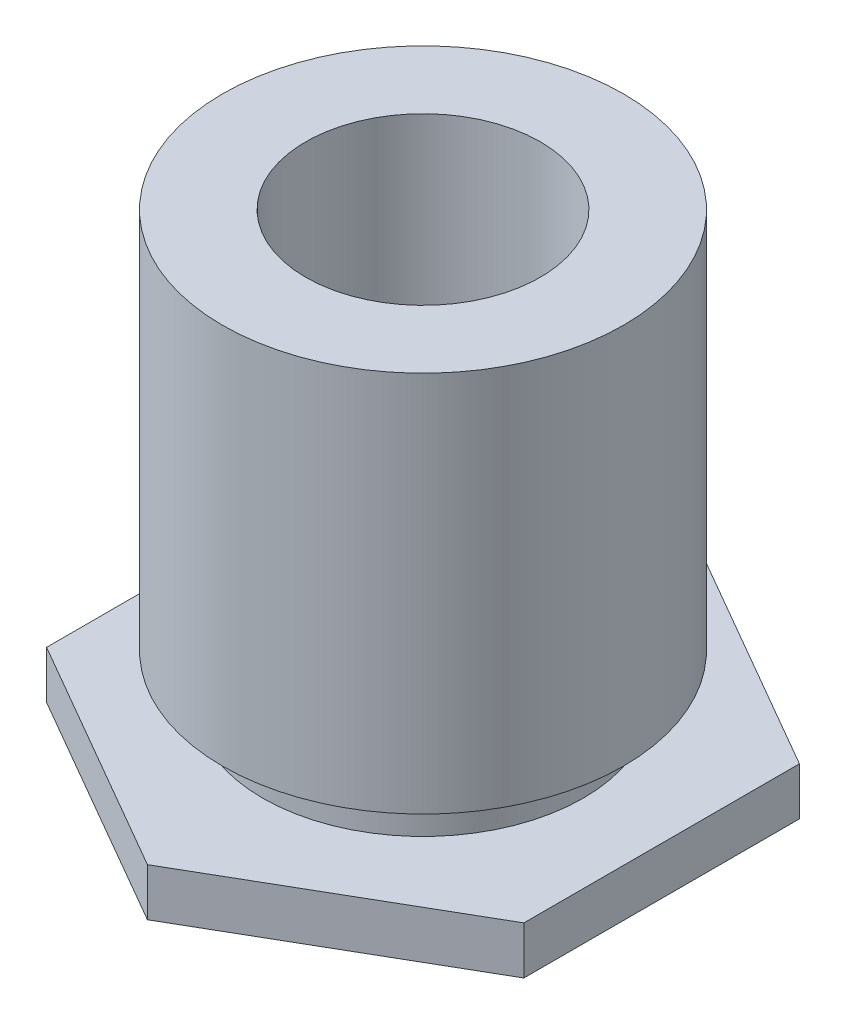
SolidWorks part; units mm, degrees
other "Детальный элемент1"
other "Детальный элемент2"
material "A2"
ref_plane "Спереди" through (0, 0, 0) normal (0, 0, 1) x (1, 0, 0)
ref_plane "Сверху" through (0, 0, 0) normal (0, 1, 0) x (1, 0, 0)
ref_plane "Справа" through (0, 0, 0) normal (1, 0, 0) x (0, 0, -1)
sketch "Эскиз1" plane through (0, 0, 0) normal (0, 1, 0) x (1, 0, 0)
  line L1 (0, -2.8868) -> (2.5, -1.4434)
  line L2 (2.5, -1.4434) -> (2.5, 1.4434)
  line L3 (2.5, 1.4434) -> (0, 2.8868)
  line L4 (0, 2.8868) -> (-2.5, 1.4434)
  line L5 (-2.5, 1.4434) -> (-2.5, -1.4434)
  line L6 (-2.5, -1.4434) -> (0, -2.8868)
  circle A0 centre (0, 0) radius 2.5 construction
  dimension "Размер шестигранника шляпки" = 5
extrude "Бобышка-Вытянуть1" add sketch "Эскиз1" along normal blind 0.5
sketch "Эскиз6" plane through (0, 0, 0) normal (0, 0, 1) x (1, 0, 0)
  line L0 (2.1, 5) -> (2.1, 1)
  line L1 (2.1, 1) -> (1.68, 1)
  line L2 (1.68, 1) -> (1.68, 0.5)
  line L3 (0, 0.5) -> (2.5, 0.5) construction
  line L4 (1.68, 0.5) -> (0, 0.5)
  line L5 (0, 0.5) -> (0, 1.8)
  line L6 (0, 1.8) -> (1.2295, 1.8)
  line L7 (1.2295, 1.8) -> (1.2295, 5)
  line L8 (1.2295, 5) -> (2.1, 5)
  line L9 (0, 1.8) -> (0, 0) construction
  line L10 (2.5, 0.5) -> (2.5, 0) construction
  line L11 (0, 0) -> (2.5, 0) construction
  dimension "D1" = 3.36
  dimension "Внешний диаметр" = 4.2
  dimension "D3" = 3.2
  dimension "D4" = 5
  dimension "D5" = 2.459
revolve "Повернуть1" add sketch "Эскиз6" angle 360 about L9
cosmetic thread "Условное изображение резьбы1" parameters "Длина резьбы"=8, "D2"=5
equation "\"D1@Эскиз6\"=\"Внешний диаметр@Эскиз6\" * 0.8"
